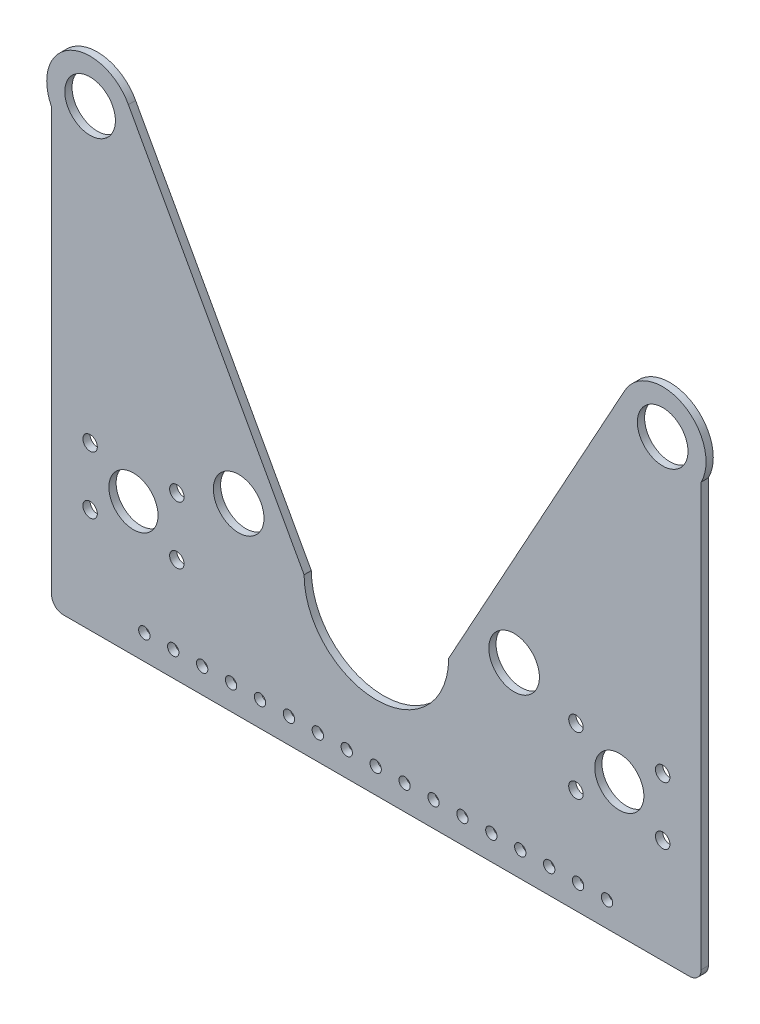
SolidWorks part; units mm, degrees
ref_plane "Front Plane" through (0, 0, 0) normal (0, 0, 1) x (1, 0, 0)
ref_plane "Top Plane" through (0, 0, 0) normal (0, 1, 0) x (1, 0, 0)
ref_plane "Right Plane" through (0, 0, 0) normal (1, 0, 0) x (0, 0, -1)
sketch "Sketch2" plane through (0, 0, 0) normal (0, 0, 1) x (1, 0, 0)
  line L0 (-106.68, -1085.9159) -> (-106.68, 48914.0841) construction
  line L1 (142.6324, 122.4629) -> (142.6324, -29.9371)
  line L2 (106.68, -1098.4025) -> (106.68, 48901.5975) construction
  line L3 (31.75, 0) -> (108.9183, 140.209)
  line L4 (0, -1082.0685) -> (0, 48917.9315) construction
  line L5 (-106.68, -44.45) -> (106.68, -44.45) construction
  line L6 (-106.68, -59.1767) -> (-106.68, -31.75)
  line L7 (0, -31.75) -> (106.68, -31.75) construction
  line L8 (106.68, -55.9582) -> (106.68, -31.75)
  line L9 (-31.75, 0) -> (-108.9183, 140.209)
  line L10 (31.75, 0) -> (108.9183, 140.209)
  line L22 (-142.6324, -57.15) -> (-142.6324, -63.0286)
  line L33 (-106.68, -31.75) -> (0, -31.75) construction
  line L34 (-142.6324, 122.4629) -> (-142.6324, -29.9371)
  line L36 (-261.1394, 46.2048) -> (-243.4617, 46.2048) construction
  line L37 (-243.4617, 46.2048) -> (-243.4617, 28.5272) construction
  line L41 (-238.3305, 62.766) -> (-266.2705, 62.766) construction
  line L42 (-233.2505, 57.686) -> (-233.2505, 17.046) construction
  line L43 (-261.1394, 46.2048) -> (-261.1394, 28.5272) construction
  line L44 (-261.1394, 28.5272) -> (-243.4617, 28.5272) construction
  line L45 (-238.3305, 11.966) -> (-266.2705, 11.966) construction
  line L46 (-271.3505, 57.686) -> (-271.3505, 17.046) construction
  line L47 (-233.2505, 62.766) -> (-271.3505, 11.966) construction
  line L48 (-125.73, 3.175) -> (-125.73, -22.225) construction
  line L49 (-1101.9372, -9.525) -> (48898.0628, -9.525) construction
  line L50 (-233.2505, 11.966) -> (-271.3505, 62.766) construction
  line L51 (-239.6005, 56.416) -> (-239.6005, 18.316) construction
  line L52 (-265.0005, 56.416) -> (-239.6005, 56.416) construction
  line L53 (-125.73, 3.175) -> (-106.68, 3.175) construction
  line L54 (-142.6324, -57.15) -> (142.6324, -57.15) construction
  line L55 (-142.6324, -29.9371) -> (-142.6324, -57.15)
  line L56 (142.6324, -29.9371) -> (142.6324, -57.15)
  line L57 (-137.5524, -68.1086) -> (137.5524, -68.1086)
  line L58 (142.6324, -63.0286) -> (142.6324, -57.15)
  arc A0 (-31.75, 0) -> (31.75, 0) centre (0, 0) ccw
  arc A1 (-108.9183, 140.209) -> (-142.6324, 122.4629) centre (-125.7268, 131.2438) ccw
  circle A2 centre (-60.4845, 12.7) radius 11.1125
  arc A3 (31.75, 0) -> (0, 31.75) centre (0, 0) ccw construction
  arc A4 (0, 31.75) -> (-31.75, 0) centre (0, 0) ccw construction
  arc A5 (137.5524, -68.1086) -> (142.6324, -63.0286) centre (137.5524, -63.0286) ccw
  arc A6 (-142.6324, -63.0286) -> (-137.5524, -68.1086) centre (-137.5524, -63.0286) ccw
  circle A7 centre (-125.7268, 131.2438) radius 11.1125
  circle A9 centre (-60.4845, 12.7) radius 19.05 construction
  circle A10 centre (60.4845, 12.7) radius 19.05 construction
  arc A11 (108.9183, 140.209) -> (142.6324, 122.4629) centre (125.7268, 131.2438) cw
  circle A12 centre (125.7268, 131.2438) radius 11.1125
  circle A34 centre (-101.9175, -57.15) radius 2.4892
  arc A40 (-142.6324, 122.4629) -> (-108.9183, 140.209) centre (-125.7268, 131.2438) ccw construction
  arc A41 (142.6324, 122.4629) -> (108.9183, 140.209) centre (125.7268, 131.2438) cw construction
  circle A42 centre (60.4845, 12.7) radius 11.1125
  circle A43 centre (-89.2175, -57.15) radius 2.4892
  circle A44 centre (-76.5175, -57.15) radius 2.4892
  circle A45 centre (-63.8175, -57.15) radius 2.4892
  circle A46 centre (-51.1175, -57.15) radius 2.4892
  circle A47 centre (-38.4175, -57.15) radius 2.4892
  circle A48 centre (-25.7175, -57.15) radius 2.4892
  circle A49 centre (-13.0175, -57.15) radius 2.4892
  circle A50 centre (-0.3175, -57.15) radius 2.4892
  circle A51 centre (12.3825, -57.15) radius 2.4892
  circle A52 centre (25.0825, -57.15) radius 2.4892
  circle A53 centre (37.7825, -57.15) radius 2.4892
  circle A54 centre (50.4825, -57.15) radius 2.4892
  circle A55 centre (63.1825, -57.15) radius 2.4892
  circle A56 centre (75.8825, -57.15) radius 2.4892
  circle A57 centre (88.5825, -57.15) radius 2.4892
  circle A58 centre (101.2825, -57.15) radius 2.4892
  circle A73 centre (-106.68, -9.525) radius 10.795
  circle A91 centre (-125.73, 3.175) radius 3.175
  circle A92 centre (-125.73, -22.225) radius 3.175
  circle A93 centre (-87.63, -22.225) radius 3.175
  circle A94 centre (-87.63, 3.175) radius 3.175
  circle A95 centre (87.63, -22.225) radius 3.175
  circle A96 centre (87.63, 3.175) radius 3.175
  circle A97 centre (106.68, -9.525) radius 10.795
  circle A98 centre (125.73, -22.225) radius 3.175
  circle A99 centre (125.73, 3.175) radius 3.175
  arc A100 (-260.1552, 27.7564) -> (-262.1235, 29.2979) centre (-261.1394, 28.5272) ccw construction
  arc A101 (-262.1235, 29.2979) -> (-260.1552, 27.7564) centre (-261.1394, 28.5272) ccw construction
  arc A102 (-244.4458, 29.2979) -> (-242.4776, 27.7564) centre (-243.4617, 28.5272) ccw construction
  arc A103 (-242.4776, 27.7564) -> (-244.4458, 29.2979) centre (-243.4617, 28.5272) ccw construction
  arc A104 (-242.4776, 45.4341) -> (-244.4458, 46.9756) centre (-243.4617, 46.2048) ccw construction
  arc A105 (-244.4458, 46.9756) -> (-242.4776, 45.4341) centre (-243.4617, 46.2048) ccw construction
  arc A106 (-262.1235, 46.9756) -> (-260.1552, 45.4341) centre (-261.1394, 46.2048) ccw construction
  arc A107 (-260.1552, 45.4341) -> (-262.1235, 46.9756) centre (-261.1394, 46.2048) ccw construction
  circle A108 centre (-252.3005, 37.366) radius 7.3172 construction
  circle A109 centre (-265.0005, 56.416) radius 3.175 construction
  circle A110 centre (-239.6005, 56.416) radius 3.175 construction
  circle A111 centre (-239.6005, 18.316) radius 3.175 construction
  circle A112 centre (-265.0005, 18.316) radius 3.175 construction
  arc A113 (-266.2705, 11.966) -> (-271.3505, 17.046) centre (-266.2705, 17.046) cw construction
  arc A114 (-233.2505, 17.046) -> (-238.3305, 11.966) centre (-238.3305, 17.046) cw construction
  arc A115 (-238.3305, 62.766) -> (-233.2505, 57.686) centre (-238.3305, 57.686) cw construction
  arc A116 (-266.2705, 62.766) -> (-271.3505, 57.686) centre (-266.2705, 57.686) ccw construction
  point P91 (0, 0)
  point P92 (142.6324, -57.8385)
  point P154 (-125.73, -9.525)
  dimension "D9" = 25.4
  dimension "D3" = 44.45
  dimension "D14" = 106.68
  dimension "D17" = 38.1
  dimension "D5" = 5.08
  dimension "D15" = 31.75
  dimension "D16" = 22.225
  dimension "D18" = 22.225
  dimension "D19" = 19.05
  dimension "D21" = 125.7268
  dimension "D27" = 22.225
  dimension "D28" = 21.59
  dimension "D33" = 6.35
  dimension "D35" = 8.8388
  dimension "D37" = 8.8388
  dimension "D46" = 6.35
  dimension "D34" = 6.35
  dimension "D36" = 1.25
  dimension "D38" = 5.08
  dimension "D1" = 28.828
  dimension "D6" = 10.9586
  dimension "D10" = 17
  dimension "D20" = 142.6324
  dimension "D25" = 152.4
  dimension "D26" = 12.7
  dimension "D32" = 6.35
  dimension "D29" = 17.6777
  dimension "D30" = 50.8
  dimension "D31" = 38.1
  dimension "D39" = 25.4
  dimension "D40" = 38.1
  dimension "D41" = 16.9024
extrude "Boss-Extrude1" add sketch "Sketch2" along normal blind 3.175 contours A11 L3 A0 L9 A1 L6 L8 A58 A57 A56 A55 region at (139.0055, 46.2629, 0)
